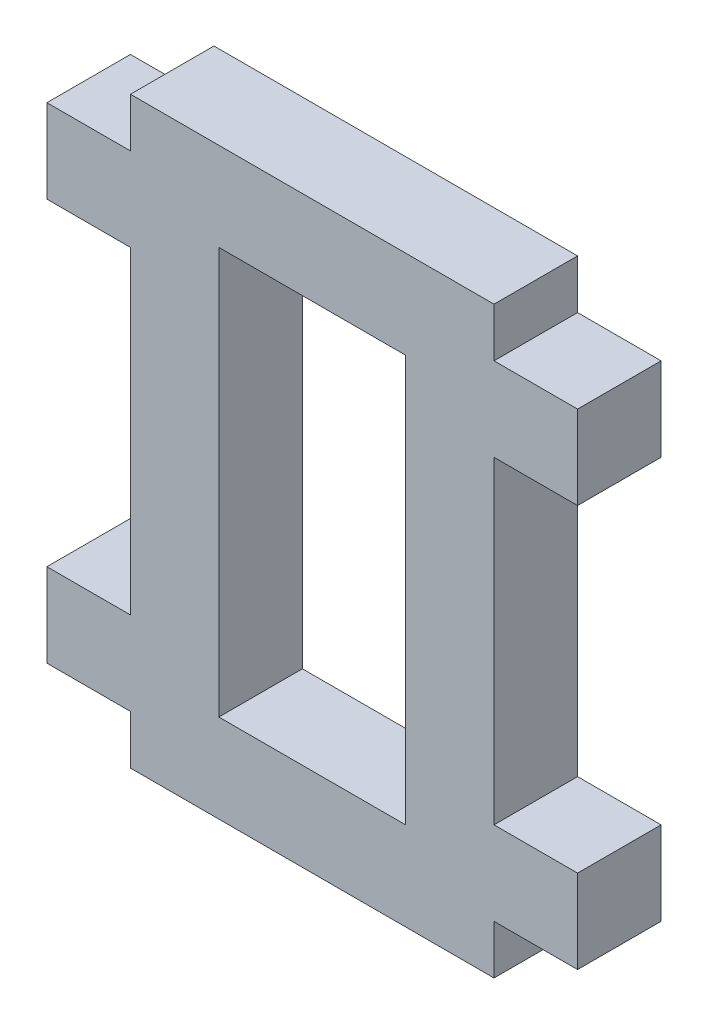
SolidWorks part; units mm, degrees
ref_plane "Front Plane" through (0, 0, 0) normal (0, 0, 1) x (1, 0, 0)
ref_plane "Top Plane" through (0, 0, 0) normal (0, 1, 0) x (1, 0, 0)
ref_plane "Right Plane" through (0, 0, 0) normal (1, 0, 0) x (0, 0, -1)
sketch "Sketch1" plane through (0, 0, 0) normal (0, 0, 1) x (1, 0, 0)
  line L0 (0, 0) -> (-13.0556, 0) construction
  line L1 (-13.0556, 20.955) -> (13.0556, 20.955)
  line L2 (-13.0556, 20.955) -> (-13.0556, -20.955)
  line L3 (-13.0556, -20.955) -> (13.0556, -20.955)
  line L4 (13.0556, 20.955) -> (13.0556, -20.955)
  line L5 (-19.0556, 17.43) -> (-13.0556, 17.43)
  line L6 (-19.0556, 17.43) -> (-19.0556, 11.43)
  line L7 (-19.0556, 11.43) -> (-13.0556, 11.43)
  line L8 (-13.0556, 17.43) -> (-13.0556, 11.43)
  line L9 (-19.0556, 17.43) -> (-13.0556, 11.43) construction
  line L10 (-19.0556, 11.43) -> (-13.0556, 17.43) construction
  line L11 (-19.0556, -11.43) -> (-13.0556, -11.43)
  line L12 (-19.0556, -17.43) -> (-19.0556, -11.43)
  line L13 (-19.0556, -17.43) -> (-13.0556, -17.43)
  line L14 (-13.0556, -17.43) -> (-13.0556, -11.43)
  line L15 (0, 0) -> (0, 20.955) construction
  line L16 (19.0556, 11.43) -> (13.0556, 11.43)
  line L17 (13.0556, 17.43) -> (13.0556, 11.43)
  line L18 (19.0556, 17.43) -> (13.0556, 17.43)
  line L19 (19.0556, 17.43) -> (19.0556, 11.43)
  line L20 (19.0556, -17.43) -> (19.0556, -11.43)
  line L21 (19.0556, -17.43) -> (13.0556, -17.43)
  line L22 (13.0556, -17.43) -> (13.0556, -11.43)
  line L23 (19.0556, -11.43) -> (13.0556, -11.43)
  point P4 (0, 20.955)
  point P6 (-13.0556, 0)
  point P7 (-16.0556, 14.43)
  point P18 (-16.0556, -11.43)
  dimension "D1" = 41.91
  dimension "D2" = 26.1112
  dimension "D3" = 6
  dimension "D4" = 22.86
extrude "Boss-Extrude1" add sketch "Sketch1" along normal blind 6 contours L6 L7 L2 L5 | L4 L1 L2 L3 | L12 L13 L2 L11 | L20 L23 L4 L21 | L19 L18 L4 L16 region at (0, 0, 0) region at (-16.0556, 14.43, 0) region at (16.0556, 14.43, 0) region at (-16.0556, -14.43, 0) region at (16.0556, -14.43, 0)
sketch "Sketch2" plane through (0, 0, 6) normal (0, 0, 1) x (1, 0, 0)
  line L49 (-6.7056, 14.605) -> (6.7056, 14.605)
  line L50 (-13.0556, 20.955) -> (13.0556, 20.955) construction
  line L51 (-13.0556, 20.955) -> (-13.0556, -20.955) construction
  line L52 (-13.0556, -20.955) -> (13.0556, -20.955) construction
  line L53 (13.0556, 20.955) -> (13.0556, -20.955) construction
  line L54 (6.7056, 14.605) -> (6.7056, -14.605)
  line L55 (-6.7056, -14.605) -> (6.7056, -14.605)
  line L56 (-6.7056, 14.605) -> (-6.7056, -14.605)
  dimension "D1" = 6.35
extrude "Cut-Extrude1" cut sketch "Sketch2" against normal through all
